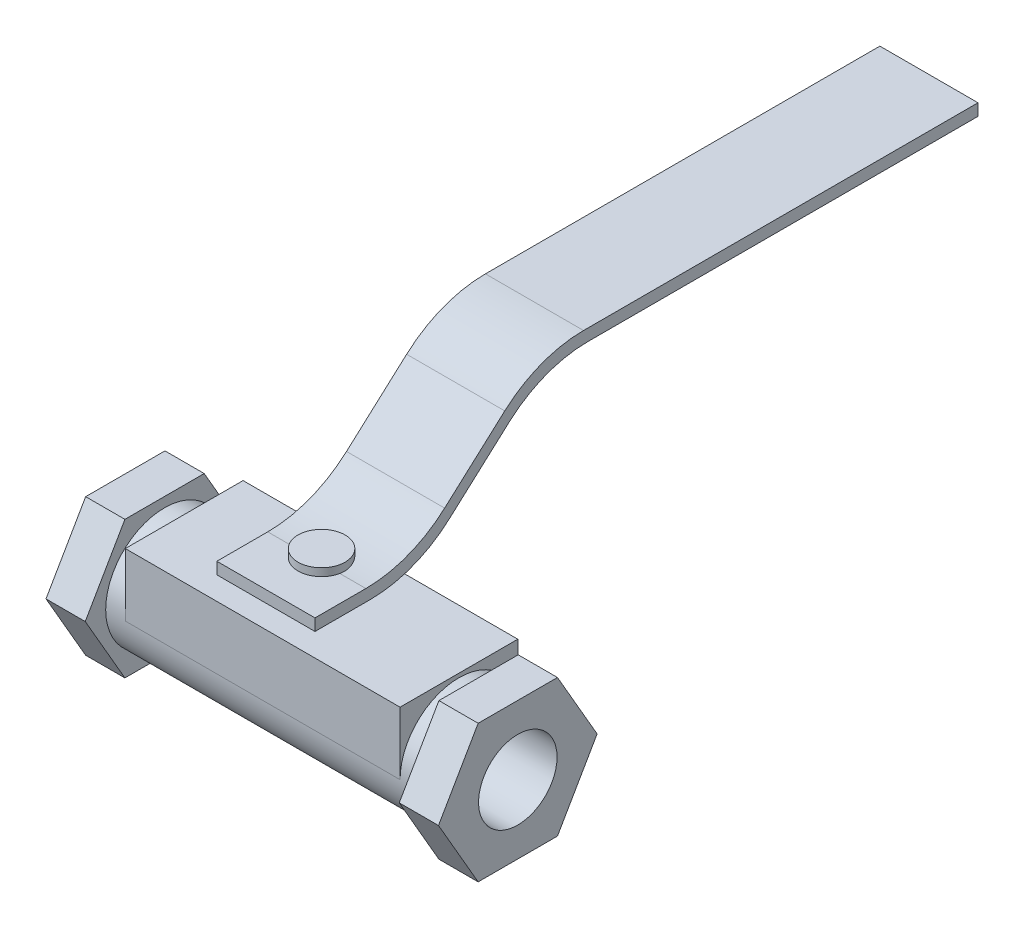
SolidWorks part; units mm, degrees
material "AISI 304"
ref_plane "Front Plane" through (0, 0, 0) normal (0, 0, 1) x (1, 0, 0)
ref_plane "Top Plane" through (0, 0, 0) normal (0, 1, 0) x (1, 0, 0)
ref_plane "Right Plane" through (0, 0, 0) normal (1, 0, 0) x (0, 0, -1)
sketch "Sketch1" plane through (0, 0, 0) normal (1, 0, 0) x (0, 0, -1)
  circle A0 centre (0, 0) radius 15
  dimension "D1" = 30
extrude "Extrude-Thin1" add sketch "Sketch1" along normal mid plane 100 thin thin type one direction reverse wall 10
sketch "Sketch2" plane through (0, 0, 0) normal (0, 1, 0) x (1, 0, 0)
  line L0 (-50, 15) -> (-50, -15) construction
  line L1 (35, -15) -> (-35, -15)
  line L2 (35, -15) -> (35, 15)
  line L3 (35, 15) -> (-35, 15)
  line L4 (-35, -15) -> (-35, 15)
  line L5 (35, -15) -> (-35, 15) construction
  line L6 (35, 15) -> (-35, -15) construction
  point P0 (0, 0)
  dimension "D1" = 15
  dimension "D2" = 30
extrude "Boss-Extrude1" add sketch "Sketch2" along normal blind 16
sketch "Sketch3" plane through (0, 16, 0) normal (0, 1, 0) x (1, 0, 0)
  circle A0 centre (0, 0) radius 6
  dimension "D1" = 12
extrude "Boss-Extrude2" add sketch "Sketch3" along normal blind 10
sketch "Sketch4" plane through (0, 0, 0) normal (1, 0, 0) x (0, 0, -1)
  line L0 (-14.1757, 24.0369) -> (10.3015, 24.0369)
  line L1 (10.3015, 24.0369) -> (42.733, 53.236)
  line L2 (42.733, 53.236) -> (154.747, 53.236)
extrude "Extrude-Thin2" add sketch "Sketch4" along normal mid plane 25 thin thin type one direction wall 3
fillet "Fillet1" radius 30 4 edges at (0, 50.236, -43.8846) (0, 21.0369, -11.453) (0, 24.0369, -10.3015) (0, 53.236, -42.733)
sketch "Sketch5" plane through (50, 0, 0) normal (1, 0, 0) x (0, 0, -1)
  line L1 (-20.2073, 0) -> (-10.1036, -17.5)
  line L2 (-10.1036, -17.5) -> (10.1036, -17.5)
  line L3 (10.1036, -17.5) -> (20.2073, 0)
  line L4 (20.2073, 0) -> (10.1036, 17.5)
  line L5 (10.1036, 17.5) -> (-10.1036, 17.5)
  line L6 (-10.1036, 17.5) -> (-20.2073, 0)
  circle A0 centre (0, 0) radius 17.5 construction
  dimension "D1" = 35
extrude "Boss-Extrude3" add sketch "Sketch5" against normal blind 10
mirror "Mirror1" about plane through (0, 0, 0) normal (1, 0, 0) of "Boss-Extrude3"
sketch "Sketch6" plane through (0, 0, 0) normal (1, 0, 0) x (0, 0, -1)
  circle A0 centre (0, 0) radius 10
  dimension "D1" = 20
extrude "Cut-Extrude1" cut sketch "Sketch6" against normal through all both and the other way through all
